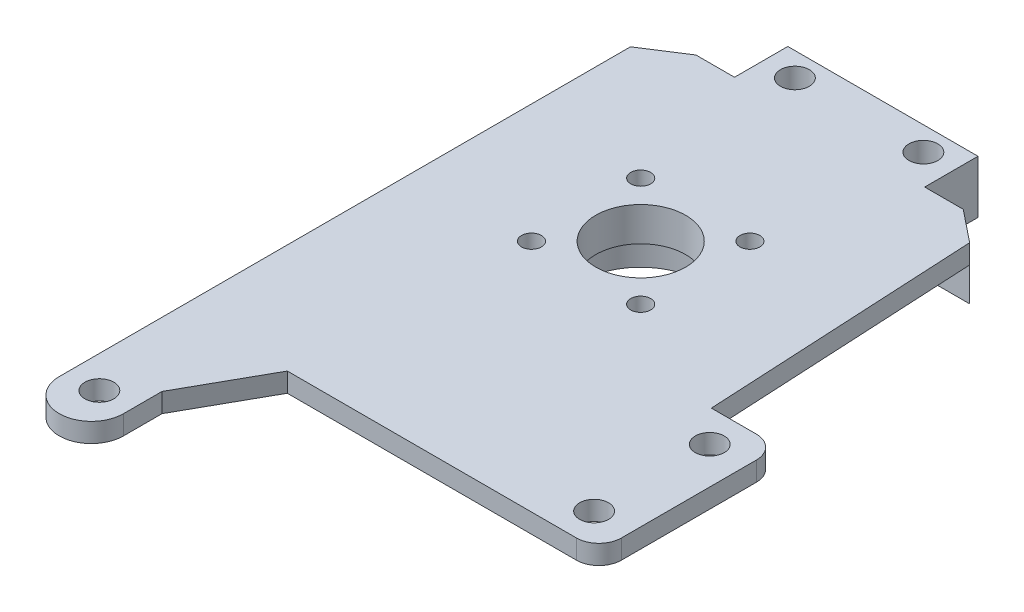
SolidWorks part; units mm, degrees
ref_plane "Front Plane" through (0, 0, 0) normal (0, 0, 1) x (1, 0, 0)
ref_plane "Top Plane" through (0, 0, 0) normal (0, 1, 0) x (1, 0, 0)
ref_plane "Right Plane" through (0, 0, 0) normal (1, 0, 0) x (0, 0, -1)
sketch "Sketch1" plane through (0, 0, 0) normal (0, 1, 0) x (1, 0, 0)
  line L0 (-10, 0) -> (10, 0) construction
  line L5 (-14.8, 3.7) -> (14.8, 3.7)
  line L6 (-14.8, 3.7) -> (-14.8, -4.6)
  line L7 (-14.8, -4.6) -> (14.8, -4.6)
  line L8 (14.8, 3.7) -> (14.8, -4.6)
  line L9 (-14.8, -4.6) -> (-20.8, -4.6)
  line L13 (20.8, -4.6) -> (14.8, -4.6)
  line L14 (-27, -8.6) -> (25.8, -8.6)
  line L28 (19, -51) -> (19, -79)
  line L29 (-24, -87.5) -> (-14.76, -87.5)
  line L30 (-27, -91.5) -> (-27, -97.5)
  line L31 (-17.6699, -96.25) -> (-19.8349, -92.5)
  line L32 (35, -79) -> (-10, -79)
  line L33 (32.75, -56) -> (32.75, -74) construction
  line L34 (19, -79) -> (28, -79)
  line L35 (28, -79) -> (28, -51)
  line L36 (28, -51) -> (19, -51)
  line L37 (19, -65) -> (-27, -65) construction
  line L38 (14, -56) -> (-8, -56) construction
  line L39 (-8, -56) -> (-8, -74) construction
  line L40 (-8, -74) -> (14, -74) construction
  line L41 (-8, -58) -> (-16, -58) construction
  line L42 (-16, -58) -> (-16, -72) construction
  line L43 (-16, -72) -> (-8, -72) construction
  line L44 (14, -56) -> (14, -74) construction
  line L45 (0, -34) -> (0, -65) construction
  line L46 (0, -34) -> (24, -34) construction
  line L47 (-24, -42.5) -> (-24, -87.5)
  line L51 (-24, -42.5) -> (-27, -42.5)
  line L52 (-27, -42.5) -> (-27, -87.5)
  line L53 (-27, -87.5) -> (-24, -87.5)
  line L54 (-19.8349, -92.5) -> (-24.1651, -92.5)
  line L55 (-27, -8.6) -> (-27, -42.5)
  line L56 (-27, -87.5) -> (-27, -91.5)
  line L57 (-27, -91.5) -> (-17, -91.5)
  line L58 (-17, -91.5) -> (-10, -79)
  line L59 (-24.1651, -92.5) -> (-26.3301, -96.25)
  line L60 (-26.3301, -96.25) -> (-24.1651, -100)
  line L61 (-24.1651, -100) -> (-19.8349, -100)
  line L62 (-24, -87.5) -> (-24, -91.5)
  line L63 (25.8, -8.6) -> (28, -51)
  line L64 (25.8, -8.6) -> (20.8, -4.6)
  line L65 (29, -76.1651) -> (32.75, -78.3301)
  line L66 (32.75, -78.3301) -> (36.5, -76.1651)
  line L67 (36.5, -76.1651) -> (36.5, -71.8349)
  line L68 (36.5, -71.8349) -> (32.75, -69.6699)
  line L69 (32.75, -69.6699) -> (29, -71.8349)
  line L70 (29, -71.8349) -> (29, -76.1651)
  line L71 (32.75, -60.3301) -> (36.5, -58.1651)
  line L72 (36.5, -58.1651) -> (36.5, -53.8349)
  line L73 (36.5, -53.8349) -> (32.75, -51.6699)
  line L74 (32.75, -51.6699) -> (29, -53.8349)
  line L75 (29, -53.8349) -> (29, -58.1651)
  line L76 (29, -58.1651) -> (32.75, -60.3301)
  line L89 (28, -65) -> (32.75, -65) construction
  line L90 (28, -51) -> (35, -51)
  line L91 (38.5, -54.5) -> (38.5, -75.5)
  line L92 (32.75, -65) -> (38.5, -65) construction
  line L93 (-19.8349, -100) -> (-17.6699, -96.25)
  line L96 (-17, -91.5) -> (-17, -97.5)
  line L97 (-27, -8.6) -> (-20.8, -4.6)
  circle A0 centre (-10, 0) radius 2.25
  circle A1 centre (10, 0) radius 2.25
  circle A14 centre (0, -34) radius 24 construction
  circle A15 centre (0, -34) radius 7
  circle A16 centre (0, -34) radius 9.6
  circle A17 centre (0, -34) radius 12.6
  circle A18 centre (32.75, -74) radius 3.75 construction
  circle A19 centre (32.75, -56) radius 3.75 construction
  circle A20 centre (-22, -96.25) radius 3.75 construction
  arc A21 (-27, -97.5) -> (-17, -97.5) centre (-22, -97.5) ccw
  circle A22 centre (32.75, -56) radius 2.25
  circle A23 centre (32.75, -74) radius 2.25
  arc A26 (35, -51) -> (38.5, -54.5) centre (35, -54.5) cw
  arc A27 (38.5, -75.5) -> (35, -79) centre (35, -75.5) cw
  circle A29 centre (-22, -96.25) radius 2.25
  point P12 (0, -4.6)
  point P17 (0, 0)
  point P28 (-16, -65)
  point P33 (-8, -65)
  point P34 (3, -56)
  point P42 (-24, -65)
  dimension "D6" = 20
  dimension "D13" = 31
  dimension "D14" = 9
  dimension "D19" = 4.5
  dimension "D9" = 19.2
  dimension "D15" = 28
  dimension "D3" = 48
  dimension "D8" = 14
  dimension "D34" = 3
  dimension "D37" = 6
  dimension "D38" = 1
  dimension "D33" = 4.5
  dimension "D31" = 7.5
  dimension "D4" = 8.3
  dimension "D5" = 29.6
  dimension "D7" = 4.6
  dimension "D10" = 6
  dimension "D11" = 34
  dimension "D12" = 30
  dimension "D16" = 18
  dimension "D17" = 22
  dimension "D18" = 4
  dimension "D20" = 6
  dimension "D21" = 3
  dimension "D22" = 14
  dimension "D23" = 5
  dimension "D24" = 90
  dimension "D25" = 3
  dimension "D26" = 7.5
  dimension "D27" = 8
  dimension "D28" = 45
  dimension "D29" = 10
  dimension "D30" = 4
  dimension "D32" = 45
  dimension "D35" = 1
  dimension "D36" = 18
  dimension "D39" = 2
  dimension "D40" = 7
  dimension "D45" = 5
extrude "Boss-Extrude1" add sketch "Sketch1" along normal blind 3 contours L61 L93 L31 L54 L59 L60 A29 | L30 A21 L96 L57 L93 L61 L60 L59 L54 L31 | L63 L14 L55 L51 L47 L29 L58 L32 L28 L36 A17 | L29 L62 L57 L58 | L62 L53 L56 L57 | L52 L53 L47 L51 | L35 L36 L28 L32 | A27 L91 A26 L90 L35 L32 L76 L75 L74 L73 L72 L71 L70 L69 L68 L67 L66 L65 | L69 L70 L65 L66 L67 L68 A23 | L75 L76 L71 L72 L73 L74 A22 | L97 L14 L64 L13 L7 L9 region at (-0.3119, 0, 6.6791) region at (-0.6, 0, 9.5618) region at (-25.5, 0, 65) region at (33.3818, 0, 65) region at (23.5, 0, 65) region at (-25.5, 0, 89.5) region at (-19.9143, 0, 89.408) region at (-25.5, 0, 91.6487) region at (-18.8516, 0, 98.0677) region at (29.1146, 0, 74) region at (30.9323, 0, 59.1484)
extrude "Boss-Extrude2" add sketch "Sketch1<23>" against normal blind 7.3 and the other way blind 3 contours A17 A16 region at (-12.2436, 0, 34)
sketch "Sketch1<23>" plane through (0, 0, 0) normal (0, 1, 0) x (1, 0, 0) same geometry as "Sketch1"
extrude "Boss-Extrude3" add sketch "Sketch1<24>" against normal blind 2.3 and the other way blind 3 contours A16 A15 region at (-9.3285, 0, 34)
sketch "Sketch1<24>" plane through (0, 0, 0) normal (0, 1, 0) x (1, 0, 0) same geometry as "Sketch1"
sketch "Sketch2" plane through (0, 0, 0) normal (0, 1, 0) x (1, 0, 0)
  line L1 (-8.5, -25.5) -> (8.5, -25.5) construction
  line L2 (-8.5, -25.5) -> (-8.5, -42.5) construction
  line L3 (-8.5, -42.5) -> (8.5, -42.5) construction
  line L4 (8.5, -25.5) -> (8.5, -42.5) construction
  circle A0 centre (0, -34) radius 7 construction
  circle A1 centre (0, -34) radius 7
  circle A2 centre (-8.5, -25.5) radius 1.55
  circle A3 centre (8.5, -25.5) radius 1.55
  circle A4 centre (8.5, -42.5) radius 1.55
  circle A5 centre (-8.5, -42.5) radius 1.55
  point P11 (0, -25.5)
  point P12 (-8.5, -34)
  dimension "D1" = 3.1
  dimension "D2" = 17
extrude "Cut-Extrude1" cut sketch "Sketch2" along normal through all both and the other way through all
extrude "Boss-Extrude4" add sketch "Sketch1<25>" against normal blind 5.25 and the other way blind 3 contours L97 L14 L64 L13 L7 L9 | L8 L5 L6 L7 A1 A0 region at (0, 0, 0.5169) region at (-0.3119, 0, 6.6791)
sketch "Sketch1<25>" plane through (0, 0, 0) normal (0, 1, 0) x (1, 0, 0) same geometry as "Sketch1"
